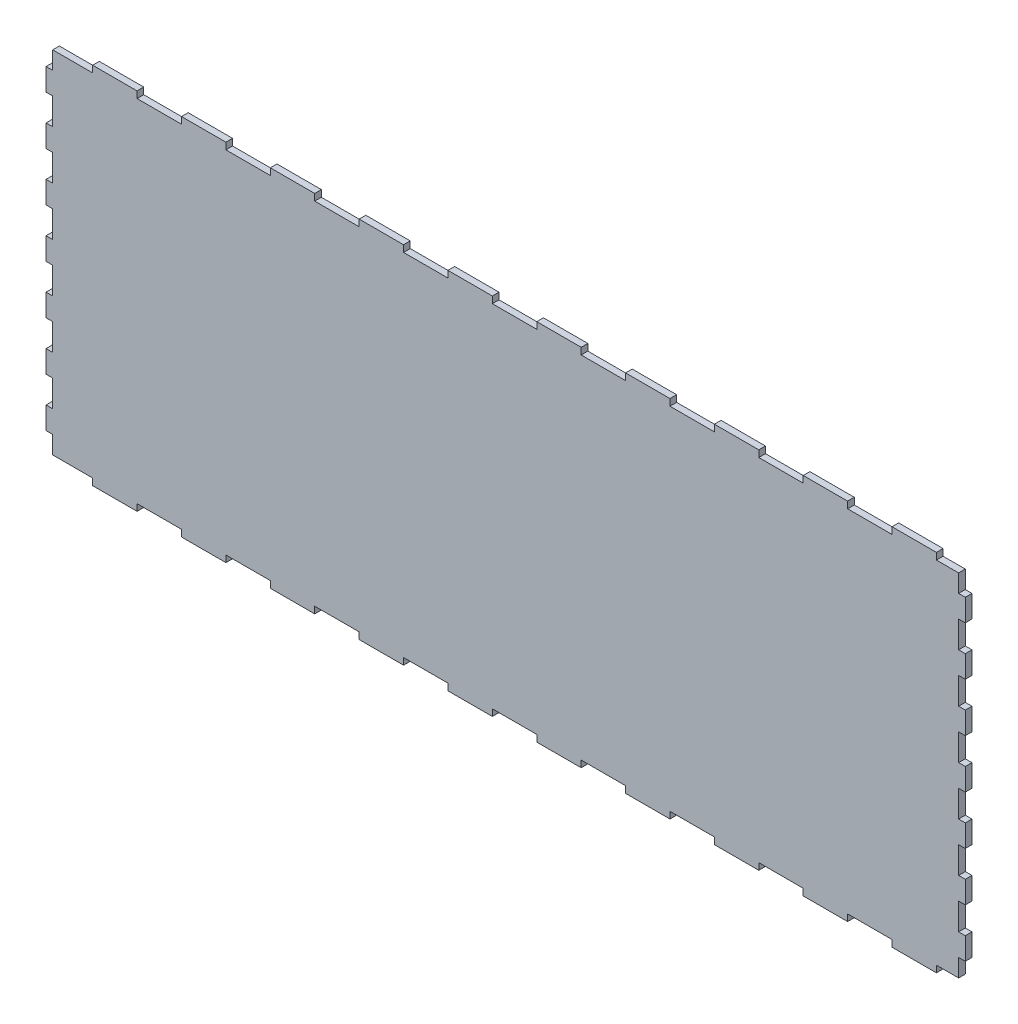
SolidWorks part; units mm, degrees
material "birch 3mm plywood"
ref_plane "Front Plane" through (0, 0, 0) normal (0, 0, 1) x (1, 0, 0)
ref_plane "Top Plane" through (0, 0, 0) normal (0, 1, 0) x (1, 0, 0)
ref_plane "Right Plane" through (0, 0, 0) normal (1, 0, 0) x (0, 0, -1)
sketch "Sketch1" plane through (0, 0, 152) normal (0, 0, 1) x (1, 0, 0)
  line L1 (-207, 82) -> (207, 82)
  line L2 (-207, 82) -> (-207, -82)
  line L3 (-207, -82) -> (207, -82)
  line L4 (207, 82) -> (207, -82)
  line L12 (200, -75) -> (-200, -75) construction
  line L13 (200, 75) -> (200, -75) construction
  line L14 (-200, -75) -> (-200, 75) construction
  line L15 (-200, 75) -> (200, 75) construction
  line L26 (-200, 0) -> (200, 0) construction
  line L31 (-200, 0) -> (200, 0) construction
  point P14 (0, 0)
  point P15 (0, 0)
  point P32 (-47.5, -25.9413)
  point P35 (256.981, -145.9413)
  point P38 (10.8894, 25.9413)
  point P51 (10.8894, -25.9413)
  point P54 (256.981, 145.9413)
  dimension "D1" = 7
  dimension "D2" = 7
  dimension "D3" = 7
  dimension "D4" = 7
  dimension "D5" = 150
  dimension "D6" = 400
extrude "Boss-Extrude1" add sketch "Sketch1" along normal blind 3
sketch "Sketch2" plane through (-207, 0, 0) normal (-1, 0, 0) x (0, 0, 1)
  line L7 (155, -82) -> (152, -82)
  line L8 (152, -82) -> (152, -71)
  line L9 (152, 82) -> (155, 82)
  line L10 (155, 82) -> (155, 71)
  line L11 (152, -61) -> (152, -49)
  line L12 (155, -71) -> (155, -82)
  line L13 (155, -49) -> (155, -61)
  line L14 (152, -39) -> (152, -27)
  line L15 (152, -17) -> (152, -5)
  line L16 (155, -27) -> (155, -39)
  line L17 (155, -5) -> (155, -17)
  line L18 (152, 5) -> (152, 17)
  line L19 (152, 27) -> (152, 39)
  line L20 (155, 17) -> (155, 5)
  line L21 (155, 39) -> (155, 27)
  line L22 (152, 49) -> (152, 61)
  line L23 (152, 71) -> (152, 82)
  line L24 (155, 61) -> (155, 49)
  line L76 (132.5, 88.6) -> (132.5, 93.6)
  line L77 (132.5, 88.6) -> (132.5, 93.6)
  line L78 (129.5, 98.6) -> (128.8771, 98.6)
  line L79 (129.5, 98.6) -> (128.8771, 98.6)
  line L80 (129.5, 82) -> (129.5, 88.6)
  line L81 (129.5, 82) -> (129.5, 88.6)
  line L82 (129.5, 88.6) -> (132.5, 88.6)
  line L83 (129.5, 88.6) -> (132.5, 88.6)
  line L85 (16, 82) -> (16, -82)
  line L102 (129.5, -82) -> (133, -82)
  line L103 (133, -82) -> (133, -79)
  line L104 (133, -79) -> (145, -79)
  line L105 (145, -79) -> (145, -82)
  line L106 (145, -82) -> (155, -82)
  line L107 (155, -82) -> (155, -71)
  line L108 (155, -71) -> (152, -71)
  line L109 (152, -71) -> (152, -61)
  line L110 (152, -61) -> (155, -61)
  line L111 (155, -61) -> (155, -49)
  line L112 (155, -49) -> (152, -49)
  line L113 (152, -49) -> (152, -39)
  line L114 (152, -39) -> (155, -39)
  line L115 (155, -39) -> (155, -27)
  line L116 (155, -27) -> (152, -27)
  line L117 (152, -27) -> (152, -17)
  line L118 (152, -17) -> (155, -17)
  line L119 (155, -17) -> (155, -5)
  line L120 (155, -5) -> (152, -5)
  line L121 (152, -5) -> (152, 5)
  line L122 (152, 5) -> (155, 5)
  line L123 (155, 5) -> (155, 17)
  line L124 (155, 17) -> (152, 17)
  line L125 (152, 17) -> (152, 27)
  line L126 (152, 27) -> (155, 27)
  line L127 (155, 27) -> (155, 39)
  line L128 (155, 39) -> (152, 39)
  line L129 (152, 39) -> (152, 49)
  line L130 (152, 49) -> (155, 49)
  line L131 (155, 49) -> (155, 61)
  line L132 (155, 61) -> (152, 61)
  line L133 (152, 61) -> (152, 71)
  line L134 (152, 71) -> (155, 71)
  line L135 (155, 71) -> (155, 82)
  line L136 (155, 82) -> (145, 82)
  line L137 (145, 82) -> (145, 79)
  line L138 (145, 79) -> (133, 79)
  line L139 (133, 79) -> (133, 82)
  line L140 (133, 82) -> (129.5, 82)
  line L184 (155, -71) -> (152, -71)
  line L186 (152, -61) -> (155, -61)
  line L188 (155, -49) -> (152, -49)
  line L190 (152, -39) -> (155, -39)
  line L192 (155, -27) -> (152, -27)
  line L194 (152, -17) -> (155, -17)
  line L196 (155, -5) -> (152, -5)
  line L198 (152, 5) -> (155, 5)
  line L200 (155, 17) -> (152, 17)
  line L202 (152, 27) -> (155, 27)
  line L204 (155, 39) -> (152, 39)
  line L206 (152, 49) -> (155, 49)
  line L208 (155, 61) -> (152, 61)
  line L210 (152, 71) -> (155, 71)
  line L297 (132.5, 93.6) -> (129.5, 93.6)
  line L298 (132.5, 93.6) -> (129.5, 93.6)
  line L299 (129.5, 93.6) -> (129.5, 98.6)
  line L300 (129.5, 93.6) -> (129.5, 98.6)
  line L301 (128.8771, -98.6) -> (129.5, -98.6)
  line L302 (128.8771, -98.6) -> (129.5, -98.6)
  line L303 (129.5, -98.6) -> (129.5, -93.6)
  line L304 (129.5, -98.6) -> (129.5, -93.6)
  line L305 (129.5, -93.6) -> (132.5, -93.6)
  line L306 (129.5, -93.6) -> (132.5, -93.6)
  line L307 (132.5, -93.6) -> (132.5, -88.6)
  line L308 (132.5, -93.6) -> (132.5, -88.6)
  line L309 (132.5, -88.6) -> (129.5, -88.6)
  line L310 (132.5, -88.6) -> (129.5, -88.6)
  line L311 (129.5, -88.6) -> (129.5, -82)
  line L312 (129.5, -88.6) -> (129.5, -82)
  arc A4 (128.8771, 98.6) -> (16, 82) centre (128.8771, -293.4723) ccw
  arc A5 (128.8771, 98.6) -> (16, 82) centre (128.8771, -293.4723) ccw
  arc A6 (16, -82) -> (128.8771, -98.6) centre (128.8771, 293.4723) ccw
  arc A7 (16, -82) -> (128.8771, -98.6) centre (128.8771, 293.4723) ccw
  line M77 (152, 82) -> (152, -82)
  line M78 (152, -82) -> (155, -82)
  line M79 (155, -82) -> (155, 82)
  line M80 (155, 82) -> (152, 82)
  dimension "D1" = 0
extrude "Cut-Extrude1" cut sketch "Sketch2" against normal blind 3 contours L184 M79 M77 M78 | L188 L186 M79 M77 | L192 L190 M79 M77 | L196 L194 M79 M77 | L200 L198 M79 M77 | L204 L202 M79 M77 | L208 L206 M79 M77 | L210 M77 M79 M80 region at (-207, -76.5, 153.5) region at (-207, -55, 153.5) region at (-207, -33, 153.5) region at (-207, -11, 153.5) region at (-207, 11, 153.5) region at (-207, 33, 153.5) region at (-207, 55, 153.5) region at (-207, 76.5, 153.5)
mirror "Mirror1" about plane through (0, 0, 0) normal (1, 0, 0) of "Cut-Extrude1"
sketch "Sketch3" plane through (0, 82, 0) normal (0, 1, 0) x (1, 0, 0)
  line L92 (174, -152) -> (194, -152)
  line L93 (194, -152) -> (194, -155)
  line L94 (194, -155) -> (204, -155)
  line L97 (207, -45) -> (204, -45)
  line L120 (204, -16) -> (-204, -16)
  line L123 (-204, -45) -> (-207, -45)
  line L146 (-204, -155) -> (-186, -155)
  line L147 (-186, -155) -> (-186, -152)
  line L148 (-186, -152) -> (-166, -152)
  line L149 (-166, -152) -> (-166, -155)
  line L150 (-166, -155) -> (-146, -155)
  line L151 (-146, -155) -> (-146, -152)
  line L152 (-146, -152) -> (-126, -152)
  line L153 (-126, -152) -> (-126, -155)
  line L154 (-126, -155) -> (-106, -155)
  line L155 (-106, -155) -> (-106, -152)
  line L156 (-106, -152) -> (-86, -152)
  line L157 (-86, -152) -> (-86, -155)
  line L158 (-86, -155) -> (-66, -155)
  line L159 (-66, -155) -> (-66, -152)
  line L160 (-66, -152) -> (-46, -152)
  line L161 (-46, -152) -> (-46, -155)
  line L162 (-46, -155) -> (-26, -155)
  line L163 (-26, -155) -> (-26, -152)
  line L164 (-26, -152) -> (-6, -152)
  line L165 (-6, -152) -> (-6, -155)
  line L166 (-6, -155) -> (14, -155)
  line L167 (14, -155) -> (14, -152)
  line L168 (14, -152) -> (34, -152)
  line L169 (34, -152) -> (34, -155)
  line L170 (34, -155) -> (54, -155)
  line L171 (54, -155) -> (54, -152)
  line L172 (54, -152) -> (74, -152)
  line L173 (74, -152) -> (74, -155)
  line L174 (74, -155) -> (94, -155)
  line L175 (94, -155) -> (94, -152)
  line L176 (94, -152) -> (114, -152)
  line L177 (114, -152) -> (114, -155)
  line L178 (114, -155) -> (134, -155)
  line L179 (134, -155) -> (134, -152)
  line L180 (134, -152) -> (154, -152)
  line L181 (154, -152) -> (154, -155)
  line L182 (154, -155) -> (174, -155)
  line L183 (174, -155) -> (174, -152)
  line L184 (174, -152) -> (194, -152)
  line L185 (194, -152) -> (194, -155)
  line L186 (194, -155) -> (204, -155)
  line L212 (204, -16) -> (-204, -16)
  line L238 (-204, -155) -> (-186, -155)
  line L239 (-186, -155) -> (-186, -152)
  line L240 (-186, -152) -> (-166, -152)
  line L241 (-166, -152) -> (-166, -155)
  line L242 (-166, -155) -> (-146, -155)
  line L243 (-146, -155) -> (-146, -152)
  line L244 (-146, -152) -> (-126, -152)
  line L245 (-126, -152) -> (-126, -155)
  line L246 (-126, -155) -> (-106, -155)
  line L247 (-106, -155) -> (-106, -152)
  line L248 (-106, -152) -> (-86, -152)
  line L249 (-86, -152) -> (-86, -155)
  line L250 (-86, -155) -> (-66, -155)
  line L251 (-66, -155) -> (-66, -152)
  line L252 (-66, -152) -> (-46, -152)
  line L253 (-46, -152) -> (-46, -155)
  line L254 (-46, -155) -> (-26, -155)
  line L255 (-26, -155) -> (-26, -152)
  line L256 (-26, -152) -> (-6, -152)
  line L257 (-6, -152) -> (-6, -155)
  line L258 (-6, -155) -> (14, -155)
  line L259 (14, -155) -> (14, -152)
  line L260 (14, -152) -> (34, -152)
  line L261 (34, -152) -> (34, -155)
  line L262 (34, -155) -> (54, -155)
  line L263 (54, -155) -> (54, -152)
  line L264 (54, -152) -> (74, -152)
  line L265 (74, -152) -> (74, -155)
  line L266 (74, -155) -> (94, -155)
  line L267 (94, -155) -> (94, -152)
  line L268 (94, -152) -> (114, -152)
  line L269 (114, -152) -> (114, -155)
  line L270 (114, -155) -> (134, -155)
  line L271 (134, -155) -> (134, -152)
  line L272 (134, -152) -> (154, -152)
  line L273 (154, -152) -> (154, -155)
  line L274 (154, -155) -> (174, -155)
  line L275 (174, -155) -> (174, -152)
  line L576 (-204, -45) -> (-207, -45)
  line L577 (-207, -45) -> (-207, -57)
  line L578 (-207, -45) -> (-207, -57)
  line L579 (-207, -57) -> (-204, -57)
  line L580 (-207, -57) -> (-204, -57)
  line L581 (-204, -57) -> (-204, -67)
  line L582 (-204, -57) -> (-204, -67)
  line L583 (-204, -67) -> (-207, -67)
  line L584 (-204, -67) -> (-207, -67)
  line L585 (-207, -67) -> (-207, -79)
  line L586 (-207, -67) -> (-207, -79)
  line L587 (-207, -79) -> (-204, -79)
  line L588 (-207, -79) -> (-204, -79)
  line L589 (-204, -79) -> (-204, -89)
  line L590 (-204, -79) -> (-204, -89)
  line L591 (-204, -89) -> (-207, -89)
  line L592 (-204, -89) -> (-207, -89)
  line L593 (-207, -89) -> (-207, -101)
  line L594 (-207, -89) -> (-207, -101)
  line L595 (-207, -101) -> (-204, -101)
  line L596 (-207, -101) -> (-204, -101)
  line L597 (-204, -101) -> (-204, -111)
  line L598 (-204, -101) -> (-204, -111)
  line L599 (-204, -111) -> (-207, -111)
  line L600 (-204, -111) -> (-207, -111)
  line L601 (-207, -111) -> (-207, -123)
  line L602 (-207, -111) -> (-207, -123)
  line L603 (-207, -123) -> (-204, -123)
  line L604 (-207, -123) -> (-204, -123)
  line L605 (-204, -123) -> (-204, -133)
  line L606 (-204, -123) -> (-204, -133)
  line L607 (-204, -133) -> (-207, -133)
  line L608 (-204, -133) -> (-207, -133)
  line L609 (-207, -133) -> (-207, -145)
  line L610 (-207, -133) -> (-207, -145)
  line L611 (-207, -145) -> (-204, -145)
  line L612 (-207, -145) -> (-204, -145)
  line L613 (-204, -145) -> (-204, -155)
  line L614 (-204, -145) -> (-204, -155)
  line L615 (-204, -16) -> (-204, -23)
  line L616 (-204, -16) -> (-204, -23)
  line L617 (-204, -23) -> (-207, -23)
  line L618 (-204, -23) -> (-207, -23)
  line L619 (-207, -23) -> (-207, -35)
  line L620 (-207, -23) -> (-207, -35)
  line L621 (-207, -35) -> (-204, -35)
  line L622 (-207, -35) -> (-204, -35)
  line L623 (-204, -35) -> (-204, -45)
  line L624 (-204, -35) -> (-204, -45)
  line L741 (207, -45) -> (204, -45)
  line L742 (204, -45) -> (204, -35)
  line L743 (204, -45) -> (204, -35)
  line L744 (204, -35) -> (207, -35)
  line L745 (204, -35) -> (207, -35)
  line L746 (207, -35) -> (207, -23)
  line L747 (207, -35) -> (207, -23)
  line L748 (207, -23) -> (204, -23)
  line L749 (207, -23) -> (204, -23)
  line L750 (204, -23) -> (204, -16)
  line L751 (204, -23) -> (204, -16)
  line L752 (204, -155) -> (204, -145)
  line L753 (204, -155) -> (204, -145)
  line L754 (204, -145) -> (207, -145)
  line L755 (204, -145) -> (207, -145)
  line L756 (207, -145) -> (207, -133)
  line L757 (207, -145) -> (207, -133)
  line L758 (207, -133) -> (204, -133)
  line L759 (207, -133) -> (204, -133)
  line L760 (204, -133) -> (204, -123)
  line L761 (204, -133) -> (204, -123)
  line L762 (204, -123) -> (207, -123)
  line L763 (204, -123) -> (207, -123)
  line L764 (207, -123) -> (207, -111)
  line L765 (207, -123) -> (207, -111)
  line L766 (207, -111) -> (204, -111)
  line L767 (207, -111) -> (204, -111)
  line L768 (204, -111) -> (204, -101)
  line L769 (204, -111) -> (204, -101)
  line L770 (204, -101) -> (207, -101)
  line L771 (204, -101) -> (207, -101)
  line L772 (207, -101) -> (207, -89)
  line L773 (207, -101) -> (207, -89)
  line L774 (207, -89) -> (204, -89)
  line L775 (207, -89) -> (204, -89)
  line L776 (204, -89) -> (204, -79)
  line L777 (204, -89) -> (204, -79)
  line L778 (204, -79) -> (207, -79)
  line L779 (204, -79) -> (207, -79)
  line L780 (207, -79) -> (207, -67)
  line L781 (207, -79) -> (207, -67)
  line L782 (207, -67) -> (204, -67)
  line L783 (207, -67) -> (204, -67)
  line L784 (204, -67) -> (204, -57)
  line L785 (204, -67) -> (204, -57)
  line L786 (204, -57) -> (207, -57)
  line L787 (204, -57) -> (207, -57)
  line L788 (207, -57) -> (207, -45)
  line L789 (207, -57) -> (207, -45)
  dimension "D1" = 0
extrude "Cut-Extrude2" cut sketch "Sketch3" against normal blind 3
mirror "Mirror2" about plane through (0, 0, 0) normal (0, 1, 0) of "Cut-Extrude2"
